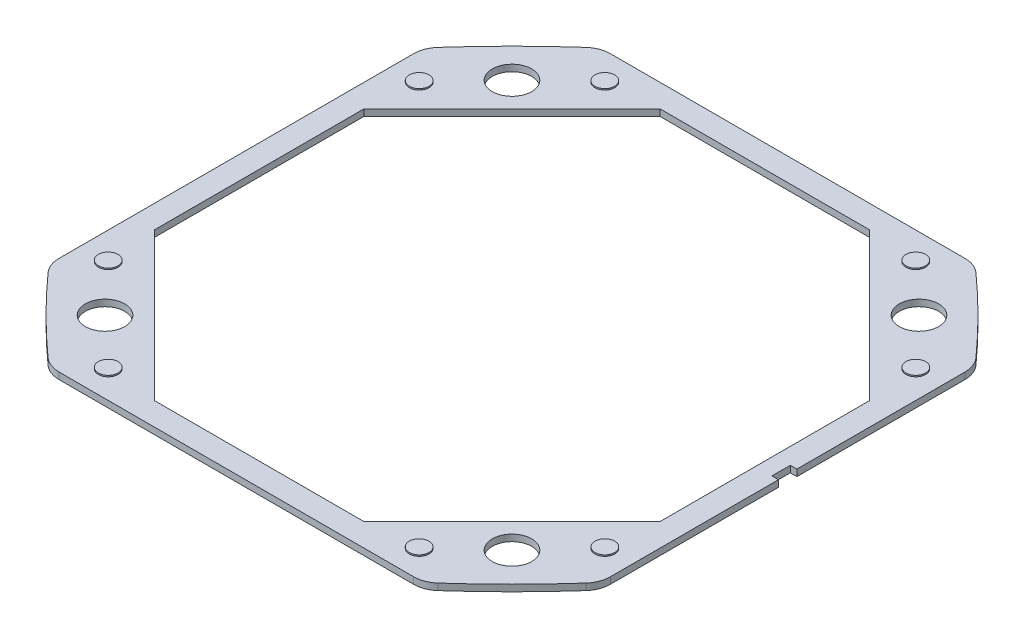
SolidWorks part; units mm, degrees
material "AISI 1020"
ref_plane "Plano frontal" through (0, 0, 0) normal (0, 0, 1) x (1, 0, 0)
ref_plane "Plano superior" through (0, 0, 0) normal (0, 1, 0) x (1, 0, 0)
ref_plane "Plano direito" through (0, 0, 0) normal (1, 0, 0) x (0, 0, -1)
sketch "Esboço1" plane through (0, 0, 0) normal (0, 1, 0) x (1, 0, 0)
  line L0 (-17.1473, 10.0763) -> (-18.9151, 11.844) construction
  line L1 (-14.2695, -21) -> (14.2695, -21)
  line L2 (-21, -14.2695) -> (-21, 14.2695)
  line L3 (-14.2695, 21) -> (14.2695, 21)
  line L4 (21, -14.2695) -> (21, -0.7)
  line L5 (-15.5, -15.5) -> (15.5, -15.5) construction
  line L6 (-15.5, -15.5) -> (-15.5, 15.5) construction
  line L7 (-15.5, 15.5) -> (15.5, 15.5) construction
  line L8 (15.5, -15.5) -> (15.5, 15.5) construction
  line L9 (21, 0.7) -> (20.5, 0.7)
  line L10 (21, -0.7) -> (20.5, -0.7)
  line L11 (20.5, -0.7) -> (20.5, 0.7)
  line L12 (-15.5, -15.5) -> (15.5, 15.5) construction
  line L13 (-15.5, 15.5) -> (15.5, -15.5) construction
  line L14 (19.25, 7.9736) -> (7.9736, 19.25)
  line L15 (7.9736, 19.25) -> (-7.9736, 19.25)
  line L16 (21, 0.7) -> (21, 14.2695)
  line L17 (-7.9736, 19.25) -> (-19.25, 7.9736)
  line L18 (-19.25, 7.9736) -> (-19.25, -7.9736)
  line L19 (-19.25, -7.9736) -> (-7.9736, -19.25)
  line L20 (-7.9736, -19.25) -> (7.9736, -19.25)
  line L21 (7.9736, -19.25) -> (19.25, -7.9736)
  line L22 (19.25, -7.9736) -> (19.25, 7.9736)
  line L23 (-10.0763, 17.1473) -> (-11.844, 18.9151) construction
  arc A0 (-21, 14.2695) -> (-14.2695, 21) centre (32.1474, -32.1474) cw
  arc A1 (14.2695, 21) -> (21, 14.2695) centre (-32.1474, -32.1474) cw
  arc A2 (21, -14.2695) -> (14.2695, -21) centre (-32.1474, 32.1474) cw
  arc A3 (-14.2695, -21) -> (-21, -14.2695) centre (32.1474, 32.1474) cw
  circle A8 centre (15.5, 15.5) radius 1.5
  circle A9 centre (-15.5, 15.5) radius 1.5
  circle A10 centre (-15.5, -15.5) radius 1.5
  circle A11 centre (15.5, -15.5) radius 1.5
  circle A12 centre (0, 0) radius 19.25 construction
  circle A13 centre (-18.9151, 11.844) radius 0.75
  circle A14 centre (-11.844, 18.9151) radius 0.75
  circle A15 centre (11.844, 18.9151) radius 0.75
  circle A16 centre (18.9151, 11.844) radius 0.75
  circle A17 centre (18.9151, -11.844) radius 0.75
  circle A18 centre (11.844, -18.9151) radius 0.75
  circle A19 centre (-11.844, -18.9151) radius 0.75
  circle A20 centre (-18.9151, -11.844) radius 0.75
  point P0 (0, 0)
  point P1 (0, 0)
  point P9 (0, 0)
  point P12 (0, 0)
  point P15 (-17.7484, 17.7484)
  point P18 (-17.7484, -17.7484)
  point P21 (17.7484, 17.7484)
  point P24 (17.7484, -17.7484)
  dimension "D2" = 31
  dimension "D4" = 3
  dimension "D12" = 1.5
  dimension "D17" = 1.4
  dimension "D22" = 28.5391
  dimension "D3" = 2.5
  dimension "D9" = 10
  dimension "D5" = 38.5
  dimension "D6" = 42
  dimension "D7" = 0.5
  dimension "D8" = 2.5
  dimension "D11" = 5
  dimension "D14" = 11.844
  dimension "D15" = 21
  dimension "D16" = 21
  dimension "D18" = 13.5695
  dimension "D19" = 13.5695
  dimension "D20" = 25.1
  dimension "D21" = 25.1
  dimension "D23" = 14.2695
  dimension "D10" = 4
  dimension "D13" = 4
extrude "Ressalto-extrusão1" add sketch "Esboço1" along normal mid plane 0.5 contours L1 A2 L4 L10 L11 L9 L16 A1 L3 A0 L2 A3 | L19 L20 L21 L22 L14 L15 L17 L18 | A10 | A11 | A8 | A9
extrude "Ressalto-extrusão2" add sketch "Esboço1<3>" along normal blind 0.1 from surface contours A20 | A13 | A14 | A19 | A15 | A16 | A17 | A18 starting at face at (6.9167, 0.25, 0)
sketch "Esboço1<3>" plane through (0, 0, 0) normal (0, 1, 0) x (1, 0, 0) same geometry as "Esboço1"
extrude "Corte-extrusão1" cut sketch "Esboço1<4>" along normal blind 0.1 from surface contours A19 | A17 | A13 | A20 | A18 | A16 | A15 | A14 region at (-18.9151, 0, -11.844) region at (18.9151, 0, 11.844) region at (-11.844, 0, 18.9151) starting at face at (15.5, -0.25, -14)
sketch "Esboço1<4>" plane through (0, 0, 0) normal (0, 1, 0) x (1, 0, 0) same geometry as "Esboço1"
fillet "Filete1" radius 2 8 edges at (21, 0, -14.2695) (14.2695, 0, -21) (-14.2695, 0, -21) (-21, 0, -14.2695) (-21, 0, 14.2695) (-14.2695, 0, 21) (14.2695, 0, 21) (21, 0, 14.2695)
